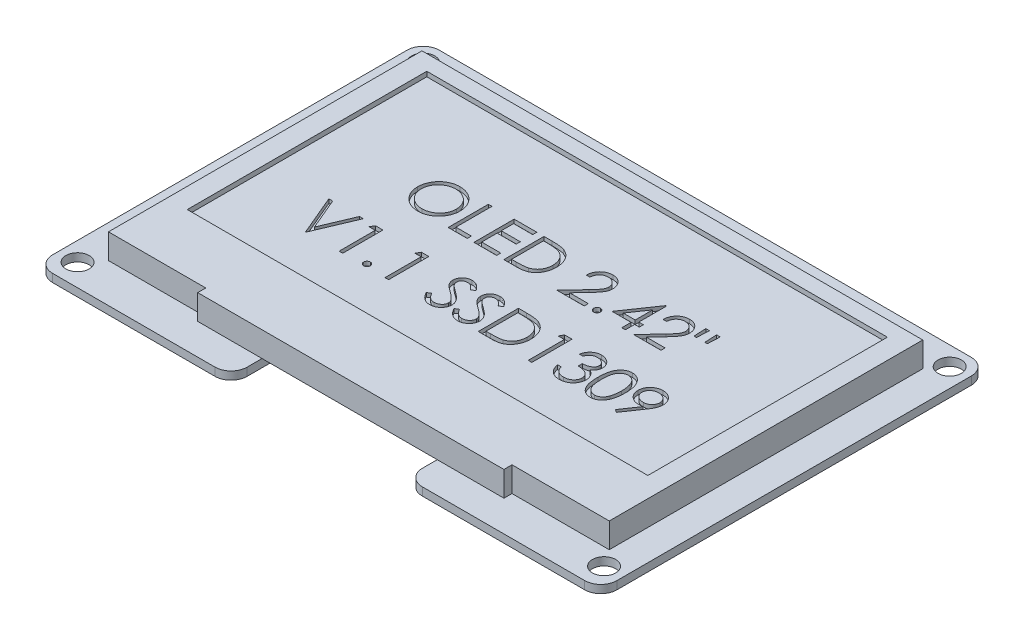
SolidWorks part; units mm, degrees
ref_plane "Front Plane" through (0, 0, 0) normal (0, 0, 1) x (1, 0, 0)
ref_plane "Top Plane" through (0, 0, 0) normal (0, 1, 0) x (1, 0, 0)
ref_plane "Right Plane" through (0, 0, 0) normal (1, 0, 0) x (0, 0, -1)
sketch "Sketch1" plane through (0, 0, 0) normal (0, 1, 0) x (1, 0, 0)
  line L0 (0, 0) -> (0, -16.82) construction
  line L1 (-33.1, -24.05) -> (-12.9, -24.05)
  line L2 (-35.1, -22.05) -> (-35.1, 22.05)
  line L3 (-33.1, 24.05) -> (33.1, 24.05)
  line L4 (35.1, -22.05) -> (35.1, 22.05)
  line L5 (-35.1, -24.05) -> (35.1, 24.05) construction
  line L6 (-35.1, 24.05) -> (35.1, -24.05) construction
  line L8 (-10.9, -22.05) -> (-10.9, -18.82)
  line L9 (-8.9, -16.82) -> (8.9, -16.82)
  line L10 (10.9, -22.05) -> (10.9, -18.82)
  line L11 (12.9, -24.05) -> (33.1, -24.05)
  arc A0 (33.1, 24.05) -> (35.1, 22.05) centre (33.1, 22.05) cw
  arc A1 (33.1, -24.05) -> (35.1, -22.05) centre (33.1, -22.05) ccw
  arc A2 (-33.1, -24.05) -> (-35.1, -22.05) centre (-33.1, -22.05) cw
  arc A3 (-35.1, 22.05) -> (-33.1, 24.05) centre (-33.1, 22.05) cw
  arc A4 (8.9, -16.82) -> (10.9, -18.82) centre (8.9, -18.82) cw
  arc A5 (-10.9, -18.82) -> (-8.9, -16.82) centre (-8.9, -18.82) cw
  arc A6 (12.9, -24.05) -> (10.9, -22.05) centre (12.9, -22.05) cw
  arc A7 (-12.9, -24.05) -> (-10.9, -22.05) centre (-12.9, -22.05) ccw
  point P0 (0, 0)
  point P28 (-10.9, -16.82)
  point P33 (-10.9, -24.05)
  dimension "D5" = 2
  dimension "D6" = 2
  dimension "D1" = 48.1
  dimension "D2" = 70.2
  dimension "D3" = 24.2
  dimension "D4" = 7.23
extrude "Boss-Extrude1" add sketch "Sketch1" along normal blind 1
sketch "Sketch2" plane through (0, 1, 0) normal (0, 1, 0) x (1, 0, 0)
  line L0 (33.1, 24.05) -> (-33.1, 24.05) construction
  line L1 (-31, 19.8) -> (31.3, 19.8)
  line L2 (-31, 19.8) -> (-31, -19.2)
  line L3 (-31, -19.2) -> (31.3, -19.2)
  line L4 (31.3, 19.8) -> (31.3, -19.2)
  line L5 (-18.9, -19.2) -> (19.2, -19.2)
  line L6 (-18.9, -19.2) -> (-18.9, -20.2)
  line L7 (-18.9, -20.2) -> (19.2, -20.2)
  line L8 (19.2, -19.2) -> (19.2, -20.2)
  line L9 (-35.1, 22.05) -> (-35.1, -22.05) construction
  line L10 (35.1, -22.05) -> (35.1, 22.05) construction
  point P8 (0.15, -19.2)
  line M12 (-10.9, -22.05) -> (-10.9, -18.82)
  arc M13 (-10.9, -18.82) -> (-8.9, -16.82) centre (-8.9, -18.82) cw
  line M14 (-8.9, -16.82) -> (8.9, -16.82)
  arc M15 (8.9, -16.82) -> (10.9, -18.82) centre (8.9, -18.82) cw
  line M16 (10.9, -18.82) -> (10.9, -22.05)
  dimension "D1" = 62.3
  dimension "D2" = 39
  dimension "D3" = 38.1
  dimension "D4" = 40
  dimension "D5" = 4.25
  dimension "D6" = 4.1
  dimension "D7" = 3.8
extrude "Boss-Extrude2" add sketch "Sketch2" along normal blind 3.1 contours L4 L1 L2 L3 M12 M13 M14 M15 M16 | L3 M12 M16 M15 M14 M13 | L7 L3 M12 M16 | L6 L7 L3 M12 | L8 L3 L7 M16 region at (0.1532, 1, -0.6866) region at (-14.9, 1, 19.7) region at (15.05, 1, 19.7) region at (0, 1, 18.0354) region at (0, 1, 19.7)
sketch "Sketch3" plane through (0, 1, 0) normal (0, 1, 0) x (1, 0, 0)
  line L0 (0, 24.05) -> (0, 0) construction
  line L1 (33.1, 24.05) -> (-33.1, 24.05) construction
  line L4 (-33.1, -24.05) -> (-12.9, -24.05) construction
  circle A0 centre (-32.75, 21.7) radius 1.45
  circle A1 centre (32.75, 21.7) radius 1.45
  circle A2 centre (32.75, -21.3) radius 1.45
  circle A3 centre (-32.75, -21.3) radius 1.45
  point P8 (0, 0)
  point P16 (0, 0)
  dimension "D1" = 2.9
  dimension "D5" = 2.75
  dimension "D2" = 43
  dimension "D3" = 65.5
  dimension "D4" = 2.35
extrude "Cut-Extrude1" cut sketch "Sketch3" against normal up to next
sketch "Sketch4" plane through (0, 0, 0) normal (0, -1, 0) x (1, 0, 0)
  line L0 (33.1, -24.05) -> (-33.1, -24.05) construction
  line L1 (8.8, -7.45) -> (-8.8, -7.45)
  line L2 (8.8, -7.45) -> (8.8, -2.85)
  line L3 (8.8, -2.85) -> (-8.8, -2.85)
  line L4 (-8.8, -7.45) -> (-8.8, -2.85)
  line L5 (0, 0) -> (0, -2.85) construction
  line L6 (-35.1, -22.05) -> (-35.1, 22.05) construction
  dimension "D1" = 17.6
  dimension "D2" = 4.6
  dimension "D3" = 16.6
  dimension "D4" = 26.3
extrude "Boss-Extrude3" add sketch "Sketch4" along normal blind 2
sketch "Sketch5" plane through (0, 0, 0) normal (0, -1, 0) x (1, 0, 0)
  line L0 (24.1, -17.75) -> (17.1, -17.75) construction
  line L1 (24.1, -19.75) -> (17.1, -19.75)
  line L2 (24.1, -15.75) -> (17.1, -15.75)
  line L3 (35.1, 22.05) -> (35.1, -22.05) construction
  line L4 (33.1, -24.05) -> (-33.1, -24.05) construction
  line L5 (0, 0) -> (0, -24.05) construction
  line L6 (-17.1, -17.75) -> (-24.1, -17.75) construction
  line L7 (-17.1, -19.75) -> (-24.1, -19.75)
  line L8 (-17.1, -15.75) -> (-24.1, -15.75)
  line L9 (-17.1, 17.85) -> (-24.1, 17.85) construction
  line L10 (-17.1, 15.85) -> (-24.1, 15.85)
  line L11 (-17.1, 19.85) -> (-24.1, 19.85)
  line L12 (24.1, 17.85) -> (17.1, 17.85) construction
  line L13 (24.1, 15.85) -> (17.1, 15.85)
  line L14 (24.1, 19.85) -> (17.1, 19.85)
  line L15 (12.9, 24.05) -> (33.1, 24.05) construction
  arc A0 (24.1, -19.75) -> (24.1, -15.75) centre (24.1, -17.75) ccw
  arc A1 (17.1, -15.75) -> (17.1, -19.75) centre (17.1, -17.75) ccw
  arc A2 (-17.1, -19.75) -> (-17.1, -15.75) centre (-17.1, -17.75) ccw
  arc A3 (-24.1, -15.75) -> (-24.1, -19.75) centre (-24.1, -17.75) ccw
  arc A4 (-17.1, 15.85) -> (-17.1, 19.85) centre (-17.1, 17.85) ccw
  arc A5 (-24.1, 19.85) -> (-24.1, 15.85) centre (-24.1, 17.85) ccw
  arc A6 (24.1, 15.85) -> (24.1, 19.85) centre (24.1, 17.85) ccw
  arc A7 (17.1, 19.85) -> (17.1, 15.85) centre (17.1, 17.85) ccw
  point P2 (20.6, -17.75)
  point P7 (26.1, -17.75)
  point P19 (-20.6, -17.75)
  point P26 (-20.6, 17.85)
  point P33 (20.6, 17.85)
  dimension "D1" = 4
  dimension "D2" = 7
  dimension "D3" = 9
  dimension "D4" = 4.3
  dimension "D7" = 4.2
  dimension "D5" = 2
  dimension "D6" = 2
extrude "Boss-Extrude4" add sketch "Sketch5" along normal blind 2
sketch "Sketch6" plane through (0, 4.1, 0) normal (0, 1, 0) x (1, 0, 0)
  line L0 (-31, 19.8) -> (31.3, 19.8) construction
  line L1 (-28.5, 17.9) -> (28.8, 17.9)
  line L2 (-28.5, 17.9) -> (-28.5, -11.9)
  line L3 (-28.5, -11.9) -> (28.8, -11.9)
  line L4 (28.8, 17.9) -> (28.8, -11.9)
  line L5 (31.3, 19.8) -> (31.3, -19.2) construction
  line L6 (-31, 19.8) -> (-31, -19.2) construction
  line L7 (-31, -19.2) -> (-18.9, -19.2) construction
  dimension "D1" = 1.9
  dimension "D2" = 2.5
  dimension "D3" = 2.5
  dimension "D4" = 7.3
  dimension "D5" = 29.8
extrude "Cut-Extrude2" cut sketch "Sketch6" against normal blind 0.6
sketch "Sketch7" plane through (0, 3.5, 0) normal (0, 1, 0) x (1, 0, 0)
  line L0 (-28.5, 3) -> (28.8, 3) construction
  line L1 (-28.5, 17.9) -> (-28.5, -11.9) construction
  line L2 (28.8, -11.9) -> (28.8, 17.9) construction
  text T0 "OLED 2.42\"\r\nV1.1 SSD1309" font "Century Gothic" height 5
extrude "Cut-Extrude3" cut sketch "Sketch7" against normal blind 0.5
sketch "Sketch8" plane through (0, 1, 0) normal (0, 1, 0) x (1, 0, 0)
  line L0 (-33.1, -24.05) -> (-12.9, -24.05) construction
  line L1 (-35.1, 22.05) -> (-35.1, -22.05) construction
  line L2 (33.1, 24.05) -> (-33.1, 24.05) construction
  line L3 (0, 0) -> (0, 24.05) construction
  circle A0 centre (-32.9, -3.75) radius 0.45
  circle A1 centre (-32.9, -1.21) radius 0.45
  circle A2 centre (-32.9, 1.33) radius 0.45
  circle A3 centre (-32.9, 3.87) radius 0.45
  circle A4 centre (-3.81, 21.85) radius 0.45
  circle A5 centre (-1.27, 21.85) radius 0.45
  circle A6 centre (1.27, 21.85) radius 0.45
  circle A7 centre (3.81, 21.85) radius 0.45
  point P25 (0, 0)
  point P26 (-2.0057, 21.85)
  dimension "D1" = 0.9
  dimension "D2" = 20.3
  dimension "D4" = 2.54
  dimension "D5" = 2.2
  dimension "D6" = 2.2
  dimension "D8" = 2.54
  dimension "D3" = 4
  dimension "D7" = 4
extrude "Cut-Extrude4" cut sketch "Sketch8" against normal through all
